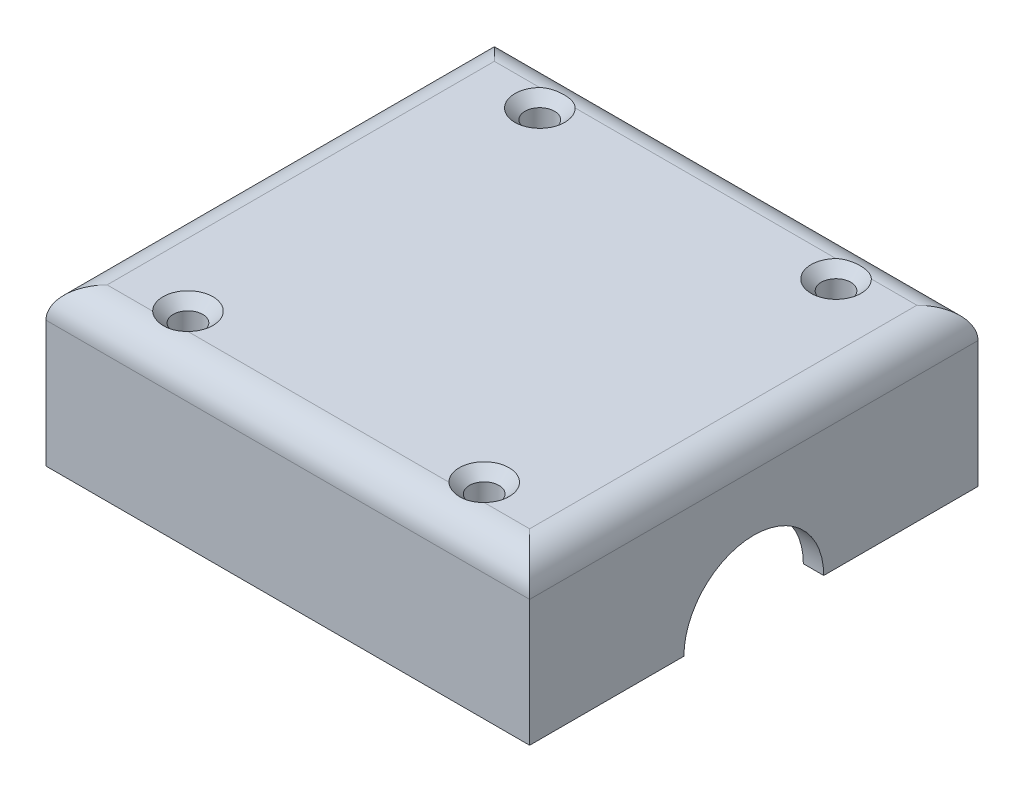
SolidWorks part; units mm, degrees
ref_plane "Front Plane" through (0, 0, 0) normal (0, 0, 1) x (1, 0, 0)
ref_plane "Top Plane" through (0, 0, 0) normal (0, 1, 0) x (1, 0, 0)
ref_plane "Right Plane" through (0, 0, 0) normal (1, 0, 0) x (0, 0, -1)
sketch "Sketch1" plane through (0, 0, 0) normal (0, 1, 0) x (1, 0, 0)
  line L1 (-23.73, -22) -> (23.73, -22)
  line L2 (-23.73, -22) -> (-23.73, 22)
  line L3 (-23.73, 22) -> (23.73, 22)
  line L4 (23.73, -22) -> (23.73, 22)
  line L5 (-23.73, -22) -> (23.73, 22) construction
  line L6 (-23.73, 22) -> (23.73, -22) construction
  line L7 (23.73, -22) -> (22.73, -22)
  line L8 (23.73, -22) -> (23.73, 22)
  line L9 (23.73, 22) -> (22.73, 22)
  point P0 (0, 0)
  dimension "D1" = 47.46
  dimension "D2" = 44
extrude "Boss-Extrude1" add sketch "Sketch1" along normal blind 15.4 contours L1 L4 L3 L2 region at (0, 0, 0)
sketch "Sketch2" plane through (0, 0, 0) normal (0, -1, 0) x (1, 0, 0)
  line L0 (-23.73, 22) -> (23.73, 22) construction
  line L1 (23.73, -22) -> (21.73, -22)
  line L2 (23.73, -22) -> (23.73, 22)
  line L3 (23.73, 22) -> (21.73, 22)
  line L4 (21.73, -22) -> (21.73, 22)
  line L5 (21.73, 0) -> (10.93, 0) construction
  line L7 (0.13, -10.91) -> (21.73, -10.91)
  line L8 (0.13, -10.91) -> (0.13, 10.91)
  line L9 (0.13, 10.91) -> (21.73, 10.91)
  line L10 (21.73, -10.91) -> (21.73, 10.91)
  line L11 (0.13, -10.91) -> (21.73, 10.91) construction
  line L12 (0.13, 10.91) -> (21.73, -10.91) construction
  dimension "D1" = 2
  dimension "D2" = 10.8
  dimension "D3" = 21.82
extrude "Cut-Extrude1" cut sketch "Sketch2" against normal blind 10.91 contours L9 L8 L7 L4 region at (10.93, 0, 0)
fillet "Fillet1" radius 10.91 2 edges at (10.93, 10.91, -10.91) (10.93, 10.91, 10.91)
sketch "Sketch4" plane through (0, 0, 0) normal (0, -1, 0) x (1, 0, 0)
  line L0 (0.13, 0) -> (-23.73, 0) construction
  line L1 (0.13, -10.91) -> (0.13, 10.91) construction
  line L2 (-23.73, 22) -> (-23.73, -22) construction
  line L8 (0.13, -10.1) -> (-23.73, -10.1)
  line L9 (0.13, -10.1) -> (0.13, 10.1)
  line L10 (0.13, 10.1) -> (-23.73, 10.1)
  line L11 (-23.73, -10.1) -> (-23.73, 10.1)
  line L12 (0.13, -10.1) -> (-23.73, 10.1) construction
  line L13 (0.13, 10.1) -> (-23.73, -10.1) construction
  point P6 (-11.8, 0)
  point P7 (-11.8, 0)
  dimension "D1" = 20.2
extrude "Cut-Extrude2" cut sketch "Sketch4" against normal blind 7.65
sketch "Sketch8" plane through (0, 0, 0) normal (0, -1, 0) x (1, 0, 0)
  line L0 (-23.73, -10.1) -> (-23.73, -22) construction
  line L1 (23.73, -22) -> (-23.73, -22)
  line L2 (23.73, -22) -> (23.73, -12.53)
  line L3 (23.73, -12.53) -> (-23.73, -12.53)
  line L4 (-23.73, -22) -> (-23.73, -12.53)
  line L5 (23.73, -17.265) -> (-23.73, -17.265) construction
  line L6 (0, -12.53) -> (0, -22) construction
  line L7 (14.535, -17.265) -> (-14.535, -17.265)
  circle A0 centre (14.535, -17.265) radius 1.45
  circle A1 centre (-14.535, -17.265) radius 1.45
  point P14 (0, -17.265)
  dimension "D3" = 2.9
  dimension "D1" = 9.47
  dimension "D2" = 29.07
extrude "Cut-Extrude3" cut sketch "Sketch8" against normal blind 20.18 contours A0 | A1 region at (-15.944, 0, -17.265) region at (14.535, 0, -15.856)
ref_plane "Plane1" through (0, 0, 0) normal (0, 0, -1) x (-1, 0, 0)
mirror "Mirror1" about plane through (0, 0, 0) normal (0, 0, -1) of "Cut-Extrude3"
chamfer "Chamfer1" distance 1 angle 45 4 edges at (14.535, 15.4, 18.715) (-14.535, 15.4, 18.715) (14.535, 15.4, -15.815) (-14.535, 15.4, -15.815)
fillet "Fillet2" radius 3 4 edges at (0, 15.4, -22) (23.73, 15.4, 0) (-23.73, 15.4, 0) (0, 15.4, 22)
sketch "Sketch9" plane through (23.73, 0, 0) normal (1, 0, 0) x (0, 0, -1)
  line L0 (-22, 0) -> (22, 0) construction
  circle A0 centre (0, 0) radius 6.86
  dimension "D1" = 13.72
extrude "Cut-Extrude4" cut sketch "Sketch9" against normal blind 2.18
sketch "Sketch10" plane through (-23.73, 0, 0) normal (-1, 0, 0) x (0, 0, 1)
  line L0 (-10.1, 7.65) -> (-7.65, 7.65)
  line L1 (10.1, 7.65) -> (-10.1, 7.65) construction
  line L2 (-10.1, 7.65) -> (-10.1, 0)
  line L3 (0, 6.82) -> (0, -6.82) construction
  line L4 (10.1, 7.65) -> (10.1, 0)
  line L5 (10.1, 7.65) -> (7.65, 7.65)
  arc A0 (-7.65, 7.65) -> (-10.1, 0) centre (-0.0495, 0.9985) ccw
  arc A1 (7.65, 7.65) -> (10.1, 0) centre (0.0495, 0.9985) cw
  line M8 (-10.1, 7.65) -> (10.1, 7.65)
  line M9 (10.1, 7.65) -> (10.1, 0)
  dimension "D2" = 10.1
  dimension "D1" = 2.45
extrude "Boss-Extrude3" add sketch "Sketch10" against normal blind 23.86 contours A1 M8 M9 | A0 L2 M8 | L4 A1 L5 region at (-23.73, 6.1138, 9.3764) region at (-23.73, 6.1138, -9.3764)
